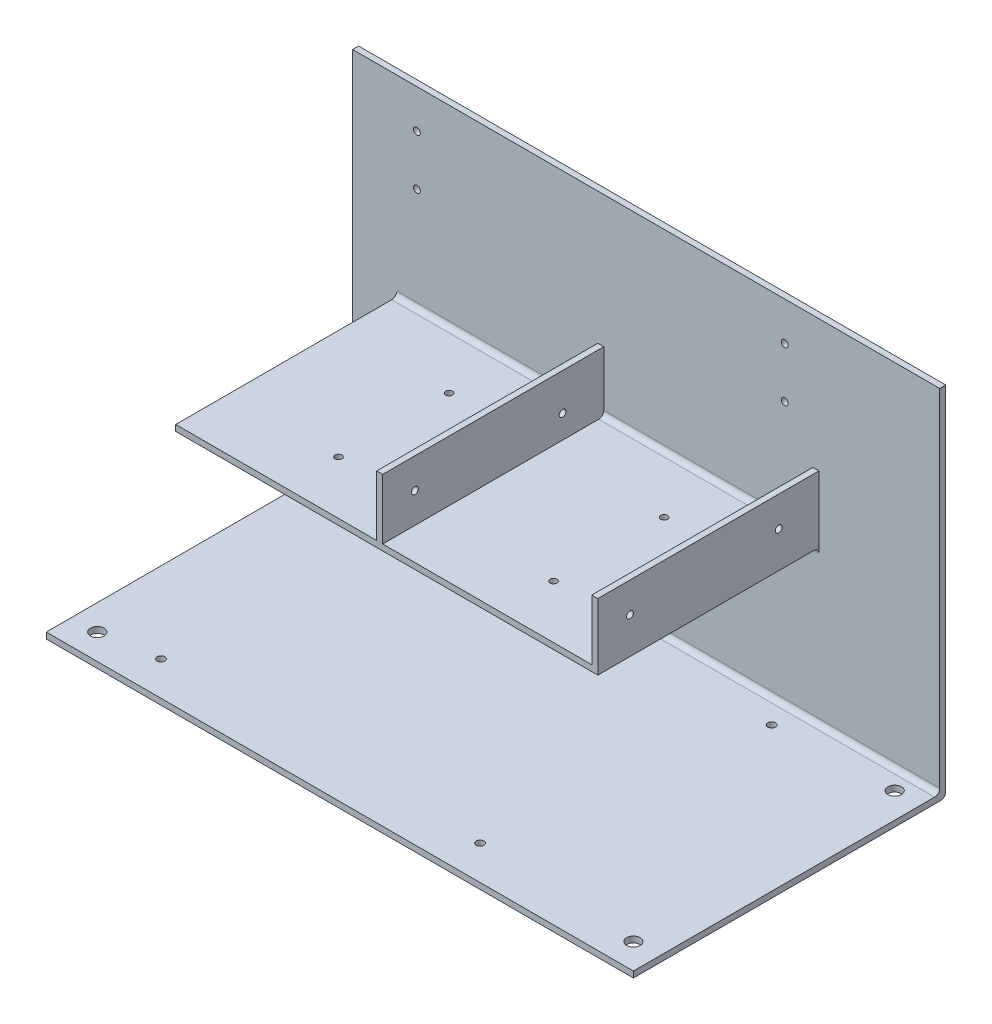
SolidWorks part; units mm, degrees
ref_plane "Front Plane" through (0, 0, 0) normal (0, 0, 1) x (1, 0, 0)
ref_plane "Top Plane" through (0, 0, 0) normal (0, 1, 0) x (1, 0, 0)
ref_plane "Right Plane" through (0, 0, 0) normal (1, 0, 0) x (0, 0, -1)
sketch "Sketch1" plane through (0, 0, 0) normal (0, 1, 0) x (1, 0, 0)
  line L1 (0, 0) -> (292.1, 0)
  line L2 (0, 0) -> (0, -152.4)
  line L3 (0, -152.4) -> (292.1, -152.4)
  line L4 (292.1, 0) -> (292.1, -152.4)
  dimension "D1" = 292.1
  dimension "D2" = 152.4
extrude "Boss-Extrude1" add sketch "Sketch1" along normal blind 3
sketch "Sketch2" plane through (0, 0, 0) normal (0, 0, -1) x (-1, 0, 0)
  line L1 (-292.1, 0) -> (0, 0)
  line L2 (-292.1, 0) -> (-292.1, 177.8)
  line L3 (-292.1, 177.8) -> (0, 177.8)
  line L4 (0, 0) -> (0, 177.8)
  point P5 (0, 0)
  dimension "D1" = 177.8
extrude "Boss-Extrude2" add sketch "Sketch2" along normal blind 3
sketch "Sketch3" plane through (0, 0, 0) normal (0, 0, 1) x (1, 0, 0)
  line L0 (25, 90.7404) -> (25, 110.8404) construction
  line L1 (22, 112.2404) -> (232, 112.2404)
  line L2 (22, 112.2404) -> (22, 79.2404)
  line L3 (22, 79.2404) -> (232, 79.2404)
  line L4 (232, 112.2404) -> (232, 79.2404)
  line L8 (172.7, 82.2404) -> (227.6, 82.2404) construction
  line L9 (229, 83.6404) -> (229, 110.8404) construction
  dimension "D1" = 3
  dimension "D2" = 3
  dimension "D3" = 3
extrude "Boss-Extrude3" add sketch "Sketch3" along normal blind 110
sketch "Sketch4" plane through (0, 0, 110) normal (0, 0, 1) x (1, 0, 0)
  line L0 (232, 112.2404) -> (22, 112.2404) construction
  line L1 (229, 82.2404) -> (125, 82.2404)
  line L2 (229, 82.2404) -> (229, 112.2404)
  line L3 (229, 112.2404) -> (125, 112.2404)
  line L4 (125, 82.2404) -> (125, 112.2404)
  line L5 (232, 79.2404) -> (232, 112.2404) construction
  line L6 (122, 82.2404) -> (22, 82.2404)
  line L7 (122, 82.2404) -> (122, 112.2404)
  line L8 (122, 112.2404) -> (22, 112.2404)
  line L9 (22, 82.2404) -> (22, 112.2404)
  line L10 (22, 79.2404) -> (232, 79.2404) construction
  line L11 (22, 79.2404) -> (232, 79.2404) construction
  line L12 (122, 83.6404) -> (122, 110.8404) construction
  line L13 (22, 112.2404) -> (22, 79.2404) construction
  dimension "D1" = 3
  dimension "D2" = 3
  dimension "D3" = 3
  dimension "D4" = 3
  dimension "D5" = 3
extrude "Cut-Extrude1" cut sketch "Sketch4" against normal blind 110
hole_wizard "#6 Clearance Hole1" positions "Sketch8" profile "Sketch9" hole size "#6" standard "ANSI Inch" end condition up to next
sketch "Sketch8" plane through (0, 0, 0) normal (0, -1, 0) x (-1, 0, 0)
  point P0 (-40.113, -11.985)
  point P4 (-40.113, -135.429)
  point P7 (-220.453, -11.985)
  point P10 (-198.863, -135.429)
sketch "Sketch9" plane through (40.113, 0, 11.985) normal (1, 0, 0) x (0, 0, -1)
  line L0 (0, 0) -> (0, 3)
  line L1 (0, 3) -> (1.8986, 3)
  line L2 (1.8986, 3) -> (1.8986, 0)
  line L5 (1.8986, 0) -> (0, 0)
  line L11 (0, -6.35) -> (0, 107.95) construction
  dimension "Thru Hole Dia." = 3.7973
  dimension "Thru Hole Depth" = 3
hole_wizard "M3 Clearance Hole1" positions "Sketch12" profile "Sketch13" hole size "M3" standard "ANSI Metric" end condition up to next
sketch "Sketch12" plane through (0, 79.2404, 0) normal (0, -1, 0) x (-1, 0, 0)
  point P0 (-76.5, -28.5)
  point P3 (-76.5, -83.5)
  point P6 (-183.5, -83.5)
  point P9 (-183.5, -28.5)
sketch "Sketch13" plane through (76.5, 79.2404, 28.5) normal (1, 0, 0) x (0, 0, -1)
  line L0 (0, 0) -> (0, 3)
  line L1 (0, 3) -> (1.7, 3)
  line L2 (1.7, 3) -> (1.7, 0)
  line L5 (1.7, 0) -> (0, 0)
  line L11 (0, -6.35) -> (0, 107.95) construction
  dimension "Thru Hole Dia." = 3.4
  dimension "Thru Hole Depth" = 3
hole_wizard "M3 Clearance Hole2" positions "Sketch14" profile "Sketch15" hole size "M3" standard "ANSI Metric" end condition up to next
sketch "Sketch14" plane through (125, 0, 0) normal (1, 0, 0) x (0, 0, -1)
  point P0 (-94, 97.2404)
  point P3 (-20.5069, 93.8291)
sketch "Sketch15" plane through (125, 97.2404, 94) normal (0, 1, 0) x (0, 0, -1)
  line L0 (0, 0) -> (0, 3)
  line L1 (0, 3) -> (1.7, 3)
  line L2 (1.7, 3) -> (1.7, 0)
  line L5 (1.7, 0) -> (0, 0)
  line L11 (0, -6.35) -> (0, 107.95) construction
  dimension "Thru Hole Dia." = 3.4
  dimension "Thru Hole Depth" = 3
hole_wizard "M3 Clearance Hole3" positions "Sketch18" profile "Sketch19" hole size "M3" standard "ANSI Metric" end condition up to next
sketch "Sketch18" plane through (232, 0, 0) normal (1, 0, 0) x (0, 0, -1)
  point P0 (-94, 97.2404)
  point P3 (-20, 97.2404)
sketch "Sketch19" plane through (232, 97.2404, 94) normal (0, 1, 0) x (0, 0, -1)
  line L0 (0, 0) -> (0, 3)
  line L1 (0, 3) -> (1.7, 3)
  line L2 (1.7, 3) -> (1.7, 0)
  line L5 (1.7, 0) -> (0, 0)
  line L11 (0, -6.35) -> (0, 107.95) construction
  dimension "Thru Hole Dia." = 3.4
  dimension "Thru Hole Depth" = 3
hole_wizard "1/4 Clearance Hole1" positions "Sketch22" profile "Sketch23" hole size "1/4" standard "ANSI Inch" end condition up to next
sketch "Sketch22" plane through (0, 3, 0) normal (0, 1, 0) x (1, 0, 0)
  line L0 (0, 0) -> (0, -152.4) construction
  line L1 (0, -152.4) -> (292.1, -152.4) construction
  line L2 (0, 3) -> (292.1, 3) construction
  line L3 (292.1, -152.4) -> (292.1, 0) construction
  point P0 (12.7, -9.7)
  point P2 (279.4, -9.7)
  point P4 (12.7, -139.7)
  point P6 (279.4, -139.7)
  dimension "D1" = 266.7
  dimension "D2" = 12.7
  dimension "D3" = 12.7
  dimension "D4" = 12.7
  dimension "D5" = 12.7
  dimension "D6" = 12.7
  dimension "D7" = 12.7
  dimension "D8" = 266.7
sketch "Sketch23" plane through (12.7, 3, 9.7) normal (1, 0, 0) x (0, 0, 1)
  line L0 (0, 0) -> (0, 3)
  line L1 (0, 3) -> (3.3782, 3)
  line L2 (3.3782, 3) -> (3.3782, 0)
  line L5 (3.3782, 0) -> (0, 0)
  line L11 (0, -6.35) -> (0, 107.95) construction
  dimension "Thru Hole Dia." = 6.7564
  dimension "Thru Hole Depth" = 3
ref_point "Point1"
ref_point "Point2"
hole_wizard "M3 Clearance Hole4" positions "Sketch24" profile "Sketch25" hole size "M3" standard "ANSI Metric" end condition up to next
sketch "Sketch24" plane through (0, 0, 0) normal (0, 0, 1) x (1, 0, 0)
  point P0 (32, 158.5904)
  point P3 (32, 133.5904)
  point P6 (215, 158.5904)
  point P9 (215, 133.5904)
sketch "Sketch25" plane through (32, 158.5904, 0) normal (1, 0, 0) x (0, -1, 0)
  line L0 (0, 0) -> (0, 3)
  line L1 (0, 3) -> (1.7, 3)
  line L2 (1.7, 3) -> (1.7, 0)
  line L5 (1.7, 0) -> (0, 0)
  line L11 (0, -6.35) -> (0, 107.95) construction
  dimension "Thru Hole Dia." = 3.4
  dimension "Thru Hole Depth" = 3
fillet "Fillet1" radius 2.54 5 edges at (177, 82.2404, 0) (72, 82.2404, 0) (146.05, 0, -3) (127, 79.2404, 0) (146.05, 3, 0)
